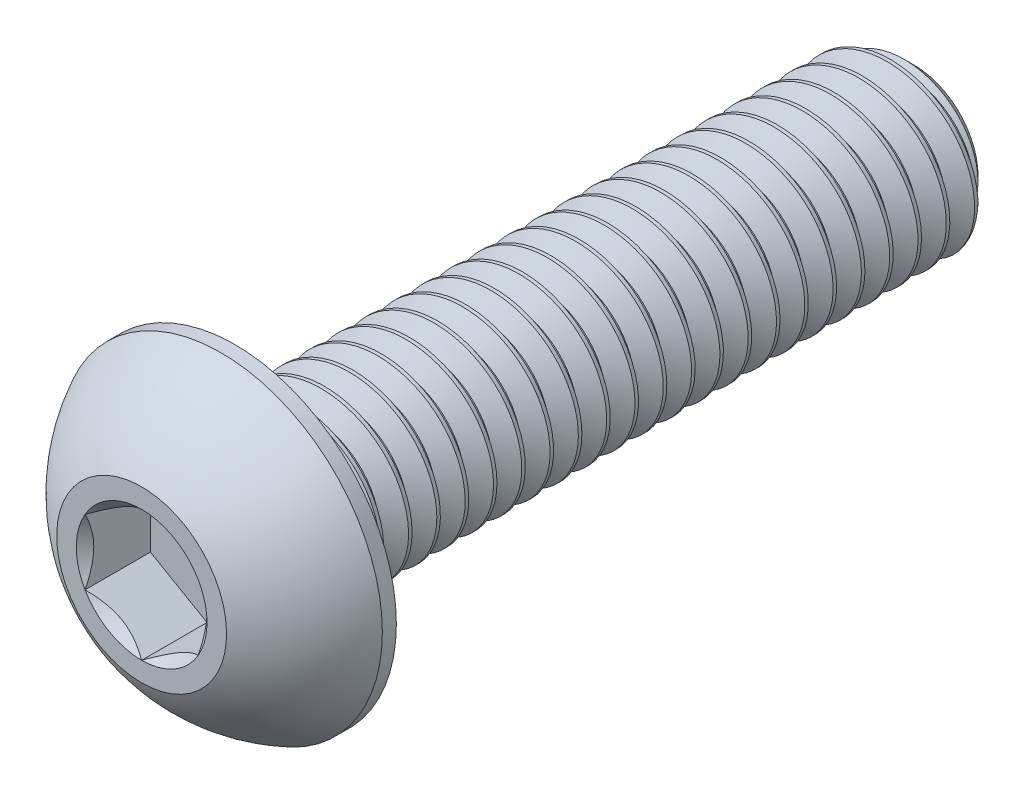
SolidWorks part; units mm, degrees
ref_plane "Front" through (0, 0, 0) normal (0, 0, 1) x (1, 0, 0)
ref_plane "Top" through (0, 0, 0) normal (0, 1, 0) x (1, 0, 0)
ref_plane "Right" through (0, 0, 0) normal (1, 0, 0) x (0, 0, -1)
sketch "Sketch1" plane through (0, 0, 0) normal (1, 0, 0) x (0, 0, -1)
  line L2 (1.65, 1.5) -> (13.65, 1.5)
  line L3 (13.65, 1.5) -> (13.65, 0)
  line L4 (13.65, 0) -> (1.65, 0)
  line L6 (1.4025, 2.85) -> (1.65, 2.85) construction
  line L7 (13.65, 1.5) -> (13.65, -1.5) construction
  line L8 (0, 0) -> (1.65, 0) construction
  line L9 (1.65, 2.85) -> (1.65, -2.85) construction
  line L11 (1.65, 1.5) -> (1.65, 0)
  line L13 (0, 1) -> (0, -1) construction
  line L14 (0, 1) -> (0, 1.5) construction
  arc A3 (0, 1.5) -> (1.4025, 2.85) centre (2.7948, 0) cw construction
  dimension "D1" = 0.2475
  dimension "Head Ht" = 1.65
  dimension "Head Dia" = 5.7
  dimension "Dia" = 3
  dimension "Lg" = 12
  dimension "Hex" = 2
revolve "Revolve1" add sketch "Sketch1" angle 360 mid plane about L4
sketch "Sketch3" plane through (0, 0, -13.65) normal (0, 0, -1) x (-1, 0, 0)
  circle A0 centre (0, 0) radius 1.5
curve "Helix/Spiral1" pitch 0.5 height 12.5 radius 1.5 centre (0, 0, -13.65) axis (0, 0, 1) start towards (0, 1, 0)
sketch "Sketch2" plane through (0, 0, 0) normal (1, 0, 0) x (0, 0, -1)
  line L0 (13.65, 1.5) -> (14.0875, 1.5)
  line L1 (14.0875, 1.5) -> (13.9, 1.1752)
  line L2 (13.9, 1.1752) -> (13.8375, 1.1752)
  line L3 (13.8375, 1.1752) -> (13.65, 1.5)
  line L4 (13.7438, 1.3376) -> (13.9938, 1.3376) construction
  dimension "D1" = 60
  dimension "D2" = 0.0625
  dimension "D3" = 0.25
chamfer "Chamfer1" distance 0.375 angle 45 1 edges at (0, 1.5, -13.65)
sweep "Cut-Sweep1" cut profiles "Sketch2" path "Helix/Spiral1"
sketch "Sketch7" plane through (0, 0, 0) normal (1, 0, 0) x (0, 0, -1)
  line L6 (1.4025, 2.85) -> (1.65, 2.85) construction
  line L8 (0, 0) -> (1.65, 0) construction
  line L11 (1.65, 2.85) -> (1.65, -2.85) construction
  line L12 (1.4025, 2.85) -> (1.65, 2.85)
  line L13 (0, 0) -> (1.65, 0)
  line L14 (0, 1) -> (0, -1) construction
  line L15 (1.65, 2.85) -> (1.65, 0)
  line L16 (0, 1.5) -> (0, 0)
  arc A2 (1.4025, 2.85) -> (0, 1.5) centre (2.7948, 0) ccw construction
  arc A3 (1.4025, 2.85) -> (0, 1.5) centre (2.7948, 0) ccw
revolve "Revolve2" add sketch "Sketch7" angle 360 mid plane about L13
sketch "Sketch5" plane through (0, 0, 0) normal (0, 0, 1) x (1, 0, 0)
  line L1 (1, -0.5774) -> (1, 0.5774)
  line L2 (1, 0.5774) -> (0, 1.1547)
  line L3 (0, 1.1547) -> (-1, 0.5774)
  line L4 (-1, 0.5774) -> (-1, -0.5774)
  line L5 (-1, -0.5774) -> (0, -1.1547)
  line L6 (0, -1.1547) -> (1, -0.5774)
  circle A0 centre (0, 0) radius 1 construction
extrude "Cut-Extrude2" cut sketch "Sketch5" against normal blind 1.155
sketch "Sketch6" plane through (0, 0, 0) normal (0, 0, 1) x (1, 0, 0)
  circle A0 centre (0, 0) radius 1.1547
extrude "Cut-Extrude3" cut sketch "Sketch6" against normal blind 1.155 draft 45
sketch "Sketch9" [suppressed] plane through (0, 0, -4.2164) normal (0, 0, 1) x (1, 0, 0)
  circle A2 centre (0, 0) radius 3.9687
extrude "Boss-Extrude2" [suppressed] add sketch "Sketch9" against normal offset from surface (9.525 mm away) 28.575 up to face at (0, 1.125, -13.65)
sketch "Sketch10" plane through (0, 0, 0) normal (1, 0, 0) x (0, 0, -1)
  line L0 (13.65, 1.5) -> (13.65, -1.5) construction
  point P0 (12.9, -1.5)
  dimension "D1" = 0.75
equation "\"D3@Helix/Spiral1\" = \"Lg@Sketch1\" + \"D4@Helix/Spiral1\""
equation "\"D2@Sketch2\" = \"D4@Helix/Spiral1\" * .125"
equation "\"D3@Sketch2\" = \"D4@Helix/Spiral1\" * .5"
equation "\"D1@Chamfer1\" = \"D4@Helix/Spiral1\" * .75"
equation "\"D1@Cut-Extrude2\" = \"Head Ht@Sketch1\" * .7"
equation "\"D1@Sketch1\" = \"Head Ht@Sketch1\" * .15"
equation "\"D1@Sketch10\" = \"D4@Helix/Spiral1\" * 1.5"
equation "\"D1@Cut-Extrude3\" = \"D1@Cut-Extrude2\""
